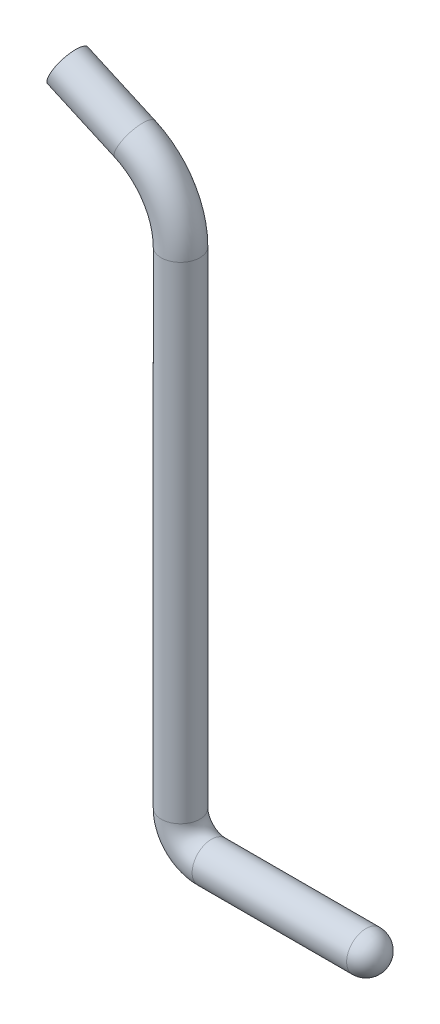
SolidWorks part; units mm, degrees
ref_plane "Front Plane" through (0, 0, 0) normal (0, 0, 1) x (1, 0, 0)
ref_plane "Top Plane" through (0, 0, 0) normal (0, 1, 0) x (1, 0, 0)
ref_plane "Right Plane" through (0, 0, 0) normal (1, 0, 0) x (0, 0, -1)
sketch "Sketch1" plane through (0, 0, 0) normal (0, 0, 1) x (1, 0, 0)
  line L0 (0, 0) -> (0, 314.65)
  line L1 (20, -20) -> (120, -20)
  line L2 (-29.5675, 360.2846) -> (-73.0117, 379.7363)
  arc A0 (0, 0) -> (20, -20) centre (20, 0) ccw
  arc A1 (0, 314.65) -> (-29.5675, 360.2846) centre (-50, 314.65) ccw
  dimension "D2" = 20
  dimension "D4" = 50
  dimension "D1" = 314.65
  dimension "D3" = 100
  dimension "D5" = 47.6
  dimension "D6" = 114.12
sweep "Sweep1" add path "Sketch1" circular profile diameter 25 parameters "D3"=25
sketch "Sketch16" plane through (0, 0, 0) normal (0, 0, 1) x (1, 0, 0)
  line L0 (120, -7.5) -> (120, -32.5)
  arc A0 (120, -7.5) -> (120, -32.5) centre (120, -20) cw
revolve "Revolve1" add sketch "Sketch16" angle 360 about L0
